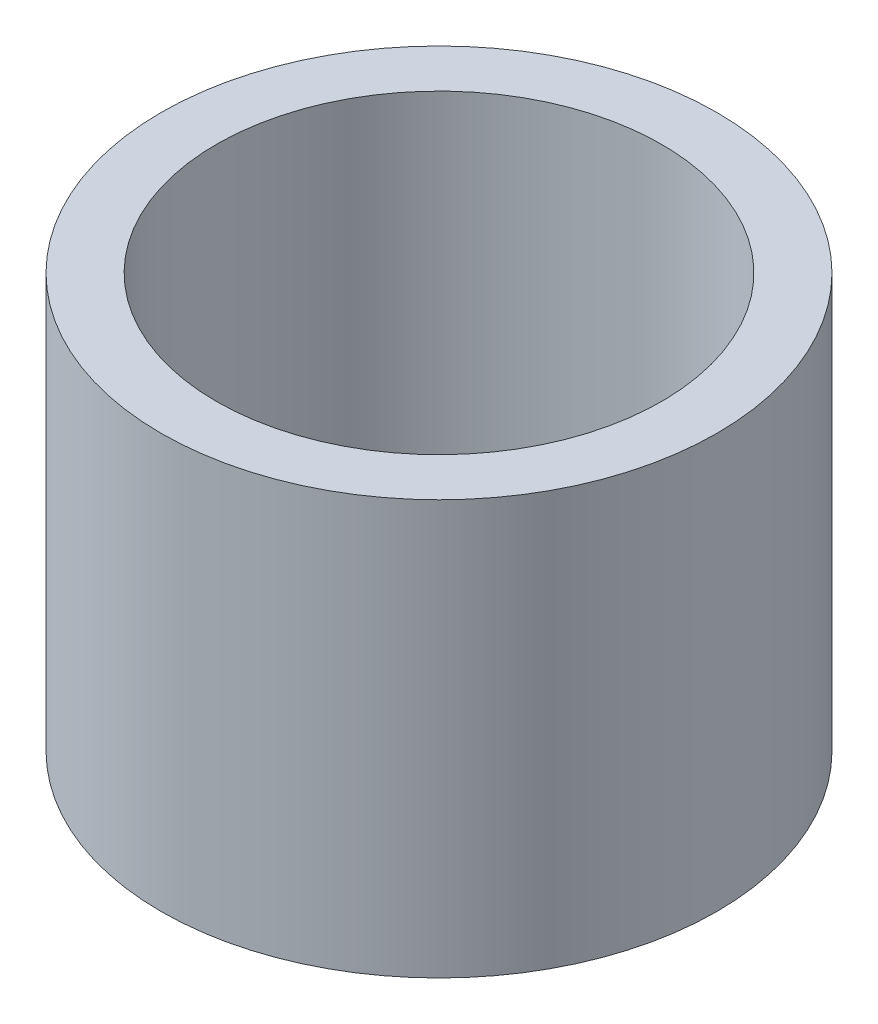
SolidWorks part; units mm, degrees
ref_plane "Front Plane" through (0, 0, 0) normal (0, 0, 1) x (1, 0, 0)
ref_plane "Top Plane" through (0, 0, 0) normal (0, 1, 0) x (1, 0, 0)
ref_plane "Right Plane" through (0, 0, 0) normal (1, 0, 0) x (0, 0, -1)
ref_axis "Axial" through (0, 3.81, 0) along (0, -1, 0)
ref_plane "Bottom Plane" through (0, -76.2, 0) normal (0, 1, 0) x (1, 0, 0)
sketch "Sketch1" plane through (0, 0, 0) normal (0, 1, 0) x (1, 0, 0)
  circle A0 centre (0, 0) radius 40.9702
  circle A1 centre (0, 0) radius 51.1302
  dimension "D1" = 102.2604
  dimension "D2" = 81.9404
extrude "Ablative" add sketch "Sketch1" against normal blind 76.2
